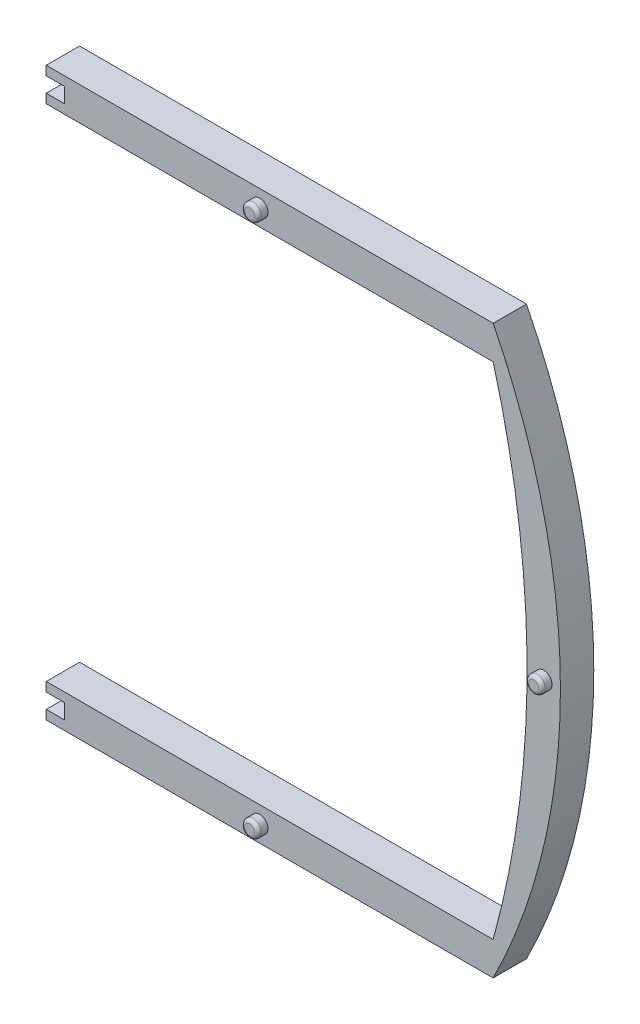
SolidWorks part; units mm, degrees
ref_plane "Plan de face" through (0, 0, 0) normal (0, 0, 1) x (1, 0, 0)
ref_plane "Plan de dessus" through (0, 0, 0) normal (0, 1, 0) x (1, 0, 0)
ref_plane "Plan de droite" through (0, 0, 0) normal (1, 0, 0) x (0, 0, -1)
sketch "Esquisse1" plane through (0, 0, 0) normal (0, 0, 1) x (1, 0, 0)
  line L1 (-32.7589, 62.5009) -> (101.2411, 62.5009)
  line L2 (-32.7589, -90.2491) -> (-27.2589, -90.2491)
  line L3 (-32.7589, -87.4991) -> (101.2411, -87.4991)
  line L4 (108.91, 0.0009) -> (111.91, 0.0009)
  line L5 (-32.7589, -90.2491) -> (-32.7589, -94.7491)
  line L6 (-32.7589, -94.7491) -> (-27.2589, -94.7491)
  line L7 (-27.2589, -90.2491) -> (-27.2589, -94.7491)
  line L8 (-32.7589, 69.7509) -> (-27.2589, 69.7509)
  line L9 (-32.7589, 69.7509) -> (-32.7589, 65.2509)
  line L10 (-32.7589, 65.2509) -> (-27.2589, 65.2509)
  line L11 (-32.7589, 62.5009) -> (101.2411, 62.5009)
  line L12 (-32.7589, 62.5009) -> (-32.7589, 72.5009)
  line L13 (-32.7589, 72.5009) -> (101.2411, 72.5009)
  line L14 (101.2411, 62.5009) -> (101.2411, 72.5009)
  line L15 (-32.7589, -87.4991) -> (101.2411, -87.4991)
  line L16 (-32.7589, -87.4991) -> (-32.7589, -97.4991)
  line L17 (-32.7589, -97.4991) -> (101.2411, -97.4991)
  line L18 (101.2411, -87.4991) -> (101.2411, -97.4991)
  line L19 (-27.2589, 69.7509) -> (-27.2589, 65.2509)
  line L20 (108.91, 0.0009) -> (108.91, -24.9991)
  line L21 (108.91, -24.9991) -> (111.91, -24.9991)
  line L22 (111.91, 0.0009) -> (111.91, -24.9991)
  circle A0 centre (116.41, -12.4991) radius 2.5
  arc A1 (101.2411, 62.5009) -> (101.2411, -87.4991) centre (-170.2522, -12.4991) cw
  arc A2 (101.2411, 72.5009) -> (101.2411, -97.4991) centre (-67.7866, -12.4991) cw
  circle A3 centre (31.2411, 67.5009) radius 2.5
  circle A4 centre (31.2411, -92.4991) radius 2.5
  point P13 (111.41, -12.4991)
  point P19 (121.41, -12.4991)
  point P30 (108.91, -12.4991)
  dimension "D17" = 25
  dimension "D1" = 134
  dimension "D2" = 150
  dimension "D3" = 134
  dimension "D4" = 4.5
  dimension "D5" = 2.75
  dimension "D6" = 2.75
  dimension "D7" = 5.5
  dimension "D8" = 5
  dimension "D9" = 5.5
  dimension "D10" = 2.75
  dimension "D11" = 10
  dimension "D12" = 4.5
  dimension "D13" = 5
  dimension "D14" = 5
  dimension "D15" = 70
  dimension "D16" = 70
  dimension "D18" = 12.5
  dimension "D19" = 4.5
  dimension "D20" = 3
  dimension "D21" = 170
  dimension "D22" = 75
extrude "Boss.-Extru.1" add sketch "Esquisse1" along normal blind 10 contours L8 L19 L10 L12 L1 L14 L13 A3 | A2 L14 A1 L18 A0 | L18 L3 L16 L2 L7 L6 L17 A4 | L4 A1 L21 L22 region at (35.5139, 67.5009, 0) region at (112.4851, -12.4991, 0) region at (111.608, -12.4991, 0) region at (35.5139, -92.4991, 0)
extrude "Boss.-Extru.2" add sketch "Esquisse1<3>" along normal blind 13 contours A3 | A0 | A4 region at (116.41, -12.4991, 0) region at (31.2411, 67.5009, 0) region at (31.2411, -92.4991, 0)
sketch "Esquisse1<3>" plane through (0, 0, 0) normal (0, 0, 1) x (1, 0, 0) same geometry as "Esquisse1"
fillet "Congé1" radius 1 3 edges at (33.7411, 67.5009, 13) (33.7411, -92.4991, 13) (118.91, -12.4991, 13)
extrude "Boss.-Extru.3" add sketch "Esquisse1<4>" along normal blind 2 contours L20 L21 L22 L4
sketch "Esquisse1<4>" plane through (0, 0, 0) normal (0, 0, 1) x (1, 0, 0) same geometry as "Esquisse1"
